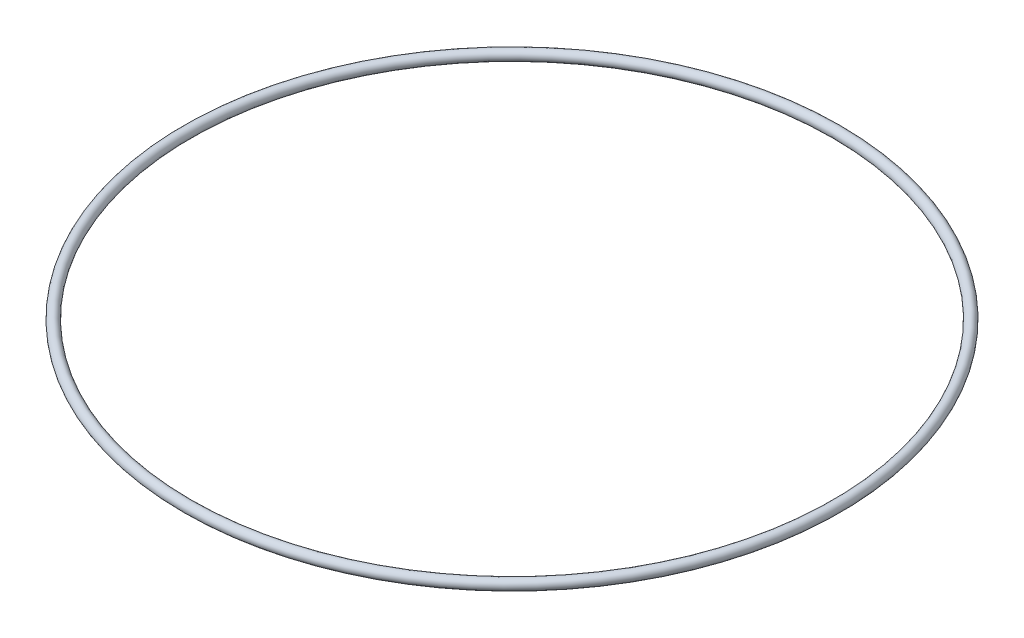
SolidWorks part; units mm, degrees
material "Silicon Rubber"
ref_plane "Front Plane" through (0, 0, 0) normal (0, 0, 1) x (1, 0, 0)
ref_plane "Top Plane" through (0, 0, 0) normal (0, 1, 0) x (1, 0, 0)
ref_plane "Right Plane" through (0, 0, 0) normal (1, 0, 0) x (0, 0, -1)
sketch "Sketch1" plane through (0, 0, 0) normal (0, 1, 0) x (1, 0, 0)
  circle A0 centre (0, 0) radius 63
  dimension "D1" = 126
sweep "Sweep1" add path "Sketch1" circular profile diameter 2 parameters "D3"=2
ref_axis "Axis1" through (0, 1.1, 0) along (0, -1, 0)
